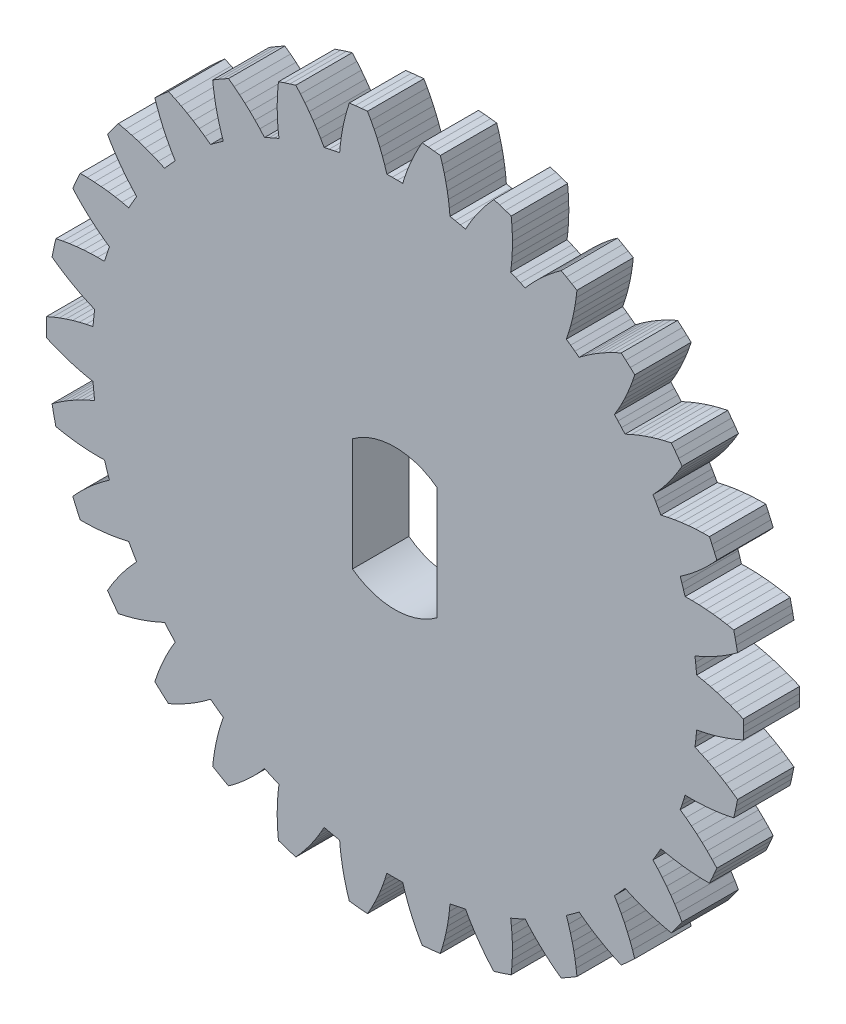
SolidWorks part; units mm, degrees
ref_plane "Front Plane" through (0, 0, 0) normal (0, 0, 1) x (1, 0, 0)
ref_plane "Top Plane" through (0, 0, 0) normal (0, 1, 0) x (1, 0, 0)
ref_plane "Right Plane" through (0, 0, 0) normal (1, 0, 0) x (0, 0, -1)
sketch "Sketch2" plane through (0, 0, 0) normal (0, 0, 1) x (1, 0, 0)
  line L20 (0.2811, 27.0228) -> (0.3553, 27.2598)
  line L21 (0.3553, 27.2598) -> (0.4378, 27.494)
  line L22 (0.4378, 27.494) -> (0.5284, 27.7252)
  line L23 (0.5284, 27.7252) -> (0.6271, 27.953)
  line L24 (0.6271, 27.953) -> (0.7337, 28.1773)
  line L25 (0.7337, 28.1773) -> (0.8481, 28.3976)
  line L26 (0.8481, 28.3976) -> (0.9702, 28.6139)
  line L27 (1.1852, 28.5951) -> (0.9702, 28.6139)
  line L28 (1.3998, 28.5725) -> (1.1852, 28.5951)
  line L29 (1.614, 28.5462) -> (1.3998, 28.5725)
  line L30 (1.614, 28.5462) -> (1.6885, 28.3093)
  line L31 (1.6885, 28.3093) -> (1.7546, 28.07)
  line L32 (1.7546, 28.07) -> (1.8122, 27.8285)
  line L33 (1.8122, 27.8285) -> (1.8614, 27.5851)
  line L34 (1.8614, 27.5851) -> (1.9019, 27.3401)
  line L35 (1.9019, 27.3401) -> (1.9339, 27.0939)
  line L36 (1.9339, 27.0939) -> (1.9572, 26.8467)
  line L37 (1.9572, 26.8467) -> (2.1412, 26.8109)
  line L38 (2.1412, 26.8109) -> (2.3246, 26.7719)
  line L39 (2.3246, 26.7719) -> (2.5072, 26.7298)
  line L41 (2.5072, 26.7298) -> (2.6291, 26.9461)
  line L42 (2.6291, 26.9461) -> (2.7584, 27.1581)
  line L43 (2.7584, 27.1581) -> (2.8951, 27.3653)
  line L44 (2.8951, 27.3653) -> (3.039, 27.5677)
  line L45 (3.039, 27.5677) -> (3.1899, 27.7649)
  line L46 (3.1899, 27.7649) -> (3.3476, 27.9567)
  line L47 (3.3476, 27.9567) -> (3.512, 28.1428)
  line L48 (3.7184, 28.0797) -> (3.512, 28.1428)
  line L49 (3.9236, 28.013) -> (3.7184, 28.0797)
  line L50 (4.1277, 27.9427) -> (3.9236, 28.013)
  line L51 (4.1277, 27.9427) -> (4.1513, 27.6955)
  line L52 (4.1513, 27.6955) -> (4.1661, 27.4477)
  line L53 (4.1661, 27.4477) -> (4.1723, 27.1995)
  line L54 (4.1723, 27.1995) -> (4.1698, 26.9512)
  line L55 (4.1698, 26.9512) -> (4.1586, 26.7031)
  line L56 (4.1586, 26.7031) -> (4.1386, 26.4556)
  line L57 (4.1386, 26.4556) -> (4.11, 26.209)
  line L58 (4.11, 26.209) -> (4.2826, 26.1357)
  line L59 (4.2826, 26.1357) -> (4.4538, 26.0595)
  line L60 (4.4538, 26.0595) -> (4.6237, 25.9803)
  line L61 (4.6237, 25.9803) -> (4.7879, 26.1666)
  line L62 (4.7879, 26.1666) -> (4.9585, 26.347)
  line L63 (4.9585, 26.347) -> (5.1353, 26.5213)
  line L64 (5.1353, 26.5213) -> (5.3181, 26.6893)
  line L65 (5.3181, 26.6893) -> (5.5067, 26.8508)
  line L66 (5.5067, 26.8508) -> (5.7008, 27.0056)
  line L67 (5.7008, 27.0056) -> (5.9003, 27.1535)
  line L68 (6.0891, 27.0489) -> (5.9003, 27.1535)
  line L69 (6.276, 26.941) -> (6.0891, 27.0489)
  line L70 (6.461, 26.8298) -> (6.276, 26.941)
  line L71 (6.461, 26.8298) -> (6.4326, 26.5831)
  line L72 (6.4326, 26.5831) -> (6.3956, 26.3376)
  line L73 (6.3956, 26.3376) -> (6.3501, 26.0935)
  line L74 (6.3501, 26.0935) -> (6.296, 25.8512)
  line L75 (6.296, 25.8512) -> (6.2334, 25.6109)
  line L76 (6.2334, 25.6109) -> (6.1625, 25.3729)
  line L77 (6.1625, 25.3729) -> (6.0832, 25.1376)
  line L78 (6.0832, 25.1376) -> (6.2368, 25.0301)
  line L79 (6.2368, 25.0301) -> (6.3884, 24.9199)
  line L80 (6.3884, 24.9199) -> (6.5381, 24.8071)
  line L81 (6.5381, 24.8071) -> (6.7374, 24.9552)
  line L82 (6.7374, 24.9552) -> (6.9418, 25.0962)
  line L83 (6.9418, 25.0962) -> (7.151, 25.23)
  line L84 (7.151, 25.23) -> (7.3648, 25.3563)
  line L85 (7.3648, 25.3563) -> (7.5828, 25.4751)
  line L86 (7.5828, 25.4751) -> (7.8049, 25.5861)
  line L87 (7.8049, 25.5861) -> (8.0307, 25.6893)
  line L88 (8.1936, 25.5477) -> (8.0307, 25.6893)
  line L89 (8.354, 25.4033) -> (8.1936, 25.5477)
  line L90 (8.5118, 25.2561) -> (8.354, 25.4033)
  line L91 (8.5118, 25.2561) -> (8.4328, 25.0207)
  line L92 (8.4328, 25.0207) -> (8.3456, 24.7882)
  line L93 (8.3456, 24.7882) -> (8.2503, 24.559)
  line L94 (8.2503, 24.559) -> (8.147, 24.3332)
  line L95 (8.147, 24.3332) -> (8.0359, 24.1111)
  line L96 (8.0359, 24.1111) -> (7.917, 23.8931)
  line L97 (7.917, 23.8931) -> (7.7905, 23.6794)
  line L98 (7.7905, 23.6794) -> (7.9184, 23.5424)
  line L99 (7.9184, 23.5424) -> (8.0438, 23.4031)
  line L100 (8.0438, 23.4031) -> (8.1668, 23.2616)
  line L101 (8.1668, 23.2616) -> (8.3925, 23.365)
  line L102 (8.3925, 23.365) -> (8.6217, 23.4604)
  line L103 (8.6217, 23.4604) -> (8.8542, 23.5478)
  line L104 (8.8542, 23.5478) -> (9.0895, 23.6269)
  line L105 (9.0895, 23.6269) -> (9.3275, 23.6977)
  line L106 (9.3275, 23.6977) -> (9.5678, 23.7602)
  line L107 (9.5678, 23.7602) -> (9.8102, 23.8141)
  line L108 (9.9401, 23.6418) -> (9.8102, 23.8141)
  line L109 (10.0669, 23.4672) -> (9.9401, 23.6418)
  line L110 (10.1907, 23.2904) -> (10.0669, 23.4672)
  line L111 (10.1907, 23.2904) -> (10.0645, 23.0766)
  line L112 (10.0645, 23.0766) -> (9.9309, 22.8673)
  line L113 (9.9309, 22.8673) -> (9.79, 22.6629)
  line L114 (9.79, 22.6629) -> (9.642, 22.4635)
  line L115 (9.642, 22.4635) -> (9.4871, 22.2694)
  line L116 (9.4871, 22.2694) -> (9.3255, 22.0809)
  line L117 (9.3255, 22.0809) -> (9.1574, 21.8981)
  line L118 (9.1574, 21.8981) -> (9.2539, 21.7375)
  line L119 (9.2539, 21.7375) -> (9.3476, 21.5751)
  line L120 (9.3476, 21.5751) -> (9.4385, 21.4112)
  line L121 (9.4385, 21.4112) -> (9.6808, 21.4654)
  line L122 (9.6808, 21.4654) -> (9.9249, 21.5111)
  line L123 (9.9249, 21.5111) -> (10.1704, 21.5482)
  line L124 (10.1704, 21.5482) -> (10.4171, 21.5767)
  line L125 (10.4171, 21.5767) -> (10.6646, 21.5965)
  line L126 (10.6646, 21.5965) -> (10.9126, 21.6076)
  line L127 (10.9126, 21.6076) -> (11.1609, 21.61)
  line L128 (11.2521, 21.4144) -> (11.1609, 21.61)
  line L129 (11.3399, 21.2172) -> (11.2521, 21.4144)
  line L130 (11.4242, 21.0186) -> (11.3399, 21.2172)
  line L131 (11.4242, 21.0186) -> (11.2563, 20.8357)
  line L132 (11.2563, 20.8357) -> (11.0821, 20.6588)
  line L133 (11.0821, 20.6588) -> (10.9017, 20.4881)
  line L134 (10.9017, 20.4881) -> (10.7155, 20.3238)
  line L135 (10.7155, 20.3238) -> (10.5237, 20.1662)
  line L136 (10.5237, 20.1662) -> (10.3264, 20.0154)
  line L137 (10.3264, 20.0154) -> (10.124, 19.8716)
  line L138 (10.124, 19.8716) -> (10.185, 19.6944)
  line L139 (10.185, 19.6944) -> (10.2429, 19.5161)
  line L140 (10.2429, 19.5161) -> (10.2977, 19.3368)
  line L141 (10.2977, 19.3368) -> (10.546, 19.3395)
  line L142 (10.546, 19.3395) -> (10.7943, 19.3334)
  line L143 (10.7943, 19.3334) -> (11.0421, 19.3187)
  line L144 (11.0421, 19.3187) -> (11.2893, 19.2952)
  line L145 (11.2893, 19.2952) -> (11.5355, 19.2631)
  line L146 (11.5355, 19.2631) -> (11.7805, 19.2224)
  line L147 (11.7805, 19.2224) -> (12.0238, 19.1732)
  line L148 (12.0724, 18.9629) -> (12.0238, 19.1732)
  line L149 (12.1172, 18.7518) -> (12.0724, 18.9629)
  line L150 (12.1584, 18.5399) -> (12.1172, 18.7518)
  line L151 (12.1584, 18.5399) -> (11.9561, 18.3959)
  line L152 (11.9561, 18.3959) -> (11.7489, 18.2591)
  line L153 (11.7489, 18.2591) -> (11.5371, 18.1297)
  line L154 (11.5371, 18.1297) -> (11.3208, 18.0077)
  line L155 (11.3208, 18.0077) -> (11.1003, 17.8934)
  line L156 (11.1003, 17.8934) -> (10.876, 17.7869)
  line L157 (10.876, 17.7869) -> (10.6481, 17.6884)
  line L158 (10.6481, 17.6884) -> (10.671, 17.5023)
  line L159 (10.671, 17.5023) -> (10.6906, 17.3159)
  line L160 (10.6906, 17.3159) -> (10.7069, 17.1291)
  line L161 (10.7069, 17.1291) -> (10.9503, 17.0801)
  line L162 (10.9503, 17.0801) -> (11.1919, 17.0226)
  line L163 (11.1919, 17.0226) -> (11.4312, 16.9566)
  line L164 (11.4312, 16.9566) -> (11.6682, 16.8823)
  line L165 (11.6682, 16.8823) -> (11.9023, 16.7997)
  line L166 (11.9023, 16.7997) -> (12.1335, 16.709)
  line L167 (12.1335, 16.709) -> (12.3613, 16.6102)
  line L168 (12.365, 16.3944) -> (12.3613, 16.6102)
  line L169 (12.365, 16.1786) -> (12.365, 16.3944)
  line L170 (12.3613, 15.9628) -> (12.365, 16.1786)
  line L171 (12.3613, 15.9628) -> (12.1335, 15.864)
  line L172 (12.1335, 15.864) -> (11.9023, 15.7733)
  line L173 (11.9023, 15.7733) -> (11.6682, 15.6907)
  line L174 (11.6682, 15.6907) -> (11.4312, 15.6164)
  line L175 (11.4312, 15.6164) -> (11.1919, 15.5504)
  line L176 (11.1919, 15.5504) -> (10.9503, 15.4929)
  line L177 (10.9503, 15.4929) -> (10.7069, 15.4438)
  line L178 (10.7069, 15.4438) -> (10.6906, 15.2571)
  line L179 (10.6906, 15.2571) -> (10.671, 15.0707)
  line L180 (10.671, 15.0707) -> (10.6481, 14.8846)
  line L181 (10.6481, 14.8846) -> (10.876, 14.7861)
  line L182 (10.876, 14.7861) -> (11.1003, 14.6796)
  line L183 (11.1003, 14.6796) -> (11.3208, 14.5653)
  line L184 (11.3208, 14.5653) -> (11.5371, 14.4433)
  line L185 (11.5371, 14.4433) -> (11.7489, 14.3139)
  line L186 (11.7489, 14.3139) -> (11.9561, 14.1771)
  line L187 (11.9561, 14.1771) -> (12.1584, 14.0331)
  line L188 (12.1172, 13.8212) -> (12.1584, 14.0331)
  line L189 (12.0724, 13.6101) -> (12.1172, 13.8212)
  line L190 (12.0238, 13.3998) -> (12.0724, 13.6101)
  line L191 (12.0238, 13.3998) -> (11.7805, 13.3506)
  line L192 (11.7805, 13.3506) -> (11.5355, 13.3098)
  line L193 (11.5355, 13.3098) -> (11.2893, 13.2778)
  line L194 (11.2893, 13.2778) -> (11.0421, 13.2543)
  line L195 (11.0421, 13.2543) -> (10.7943, 13.2396)
  line L196 (10.7943, 13.2396) -> (10.546, 13.2335)
  line L197 (10.546, 13.2335) -> (10.2977, 13.2362)
  line L198 (10.2977, 13.2362) -> (10.2429, 13.0569)
  line L199 (10.2429, 13.0569) -> (10.185, 12.8786)
  line L200 (10.185, 12.8786) -> (10.124, 12.7014)
  line L201 (10.124, 12.7014) -> (10.3264, 12.5576)
  line L202 (10.3264, 12.5576) -> (10.5237, 12.4068)
  line L203 (10.5237, 12.4068) -> (10.7155, 12.2492)
  line L204 (10.7155, 12.2492) -> (10.9017, 12.0849)
  line L205 (10.9017, 12.0849) -> (11.0821, 11.9142)
  line L206 (11.0821, 11.9142) -> (11.2563, 11.7373)
  line L207 (11.2563, 11.7373) -> (11.4242, 11.5544)
  line L208 (11.3399, 11.3558) -> (11.4242, 11.5544)
  line L209 (11.2521, 11.1586) -> (11.3399, 11.3558)
  line L210 (11.1609, 10.963) -> (11.2521, 11.1586)
  line L211 (11.1609, 10.963) -> (10.9126, 10.9654)
  line L212 (10.9126, 10.9654) -> (10.6646, 10.9765)
  line L213 (10.6646, 10.9765) -> (10.4171, 10.9963)
  line L214 (10.4171, 10.9963) -> (10.1704, 11.0248)
  line L215 (10.1704, 11.0248) -> (9.9249, 11.0619)
  line L216 (9.9249, 11.0619) -> (9.6808, 11.1076)
  line L217 (9.6808, 11.1076) -> (9.4385, 11.1618)
  line L218 (9.4385, 11.1618) -> (9.3476, 10.9979)
  line L219 (9.3476, 10.9979) -> (9.2539, 10.8355)
  line L220 (9.2539, 10.8355) -> (9.1574, 10.6748)
  line L221 (9.1574, 10.6748) -> (9.3255, 10.4921)
  line L222 (9.3255, 10.4921) -> (9.4871, 10.3036)
  line L223 (9.4871, 10.3036) -> (9.642, 10.1095)
  line L224 (9.642, 10.1095) -> (9.79, 9.9101)
  line L225 (9.79, 9.9101) -> (9.9309, 9.7057)
  line L226 (9.9309, 9.7057) -> (10.0645, 9.4964)
  line L227 (10.0645, 9.4964) -> (10.1907, 9.2826)
  line L228 (10.0669, 9.1058) -> (10.1907, 9.2826)
  line L229 (9.9401, 8.9312) -> (10.0669, 9.1058)
  line L230 (9.8102, 8.7589) -> (9.9401, 8.9312)
  line L231 (9.8102, 8.7589) -> (9.5678, 8.8128)
  line L232 (9.5678, 8.8128) -> (9.3275, 8.8753)
  line L233 (9.3275, 8.8753) -> (9.0895, 8.9461)
  line L234 (9.0895, 8.9461) -> (8.8542, 9.0252)
  line L235 (8.8542, 9.0252) -> (8.6217, 9.1126)
  line L236 (8.6217, 9.1126) -> (8.3925, 9.208)
  line L237 (8.3925, 9.208) -> (8.1668, 9.3114)
  line L238 (8.1668, 9.3114) -> (8.0438, 9.1699)
  line L239 (8.0438, 9.1699) -> (7.9184, 9.0306)
  line L240 (7.9184, 9.0306) -> (7.7905, 8.8936)
  line L241 (7.7905, 8.8936) -> (7.917, 8.6799)
  line L242 (7.917, 8.6799) -> (8.0359, 8.4619)
  line L243 (8.0359, 8.4619) -> (8.147, 8.2398)
  line L244 (8.147, 8.2398) -> (8.2503, 8.014)
  line L245 (8.2503, 8.014) -> (8.3456, 7.7848)
  line L246 (8.3456, 7.7848) -> (8.4328, 7.5523)
  line L247 (8.4328, 7.5523) -> (8.5118, 7.3169)
  line L248 (8.354, 7.1697) -> (8.5118, 7.3169)
  line L249 (8.1936, 7.0253) -> (8.354, 7.1697)
  line L250 (8.0307, 6.8837) -> (8.1936, 7.0253)
  line L251 (8.0307, 6.8837) -> (7.8049, 6.9869)
  line L252 (7.8049, 6.9869) -> (7.5828, 7.0979)
  line L253 (7.5828, 7.0979) -> (7.3647, 7.2167)
  line L254 (7.3647, 7.2167) -> (7.151, 7.343)
  line L255 (7.151, 7.343) -> (6.9418, 7.4768)
  line L256 (6.9418, 7.4768) -> (6.7374, 7.6178)
  line L257 (6.7374, 7.6178) -> (6.5381, 7.7659)
  line L258 (6.5381, 7.7659) -> (6.3884, 7.6531)
  line L259 (6.3884, 7.6531) -> (6.2368, 7.5429)
  line L260 (6.2368, 7.5429) -> (6.0832, 7.4354)
  line L261 (6.0832, 7.4354) -> (6.1625, 7.2)
  line L262 (6.1625, 7.2) -> (6.2334, 6.9621)
  line L263 (6.2334, 6.9621) -> (6.296, 6.7218)
  line L264 (6.296, 6.7218) -> (6.3501, 6.4795)
  line L265 (6.3501, 6.4795) -> (6.3956, 6.2354)
  line L266 (6.3956, 6.2354) -> (6.4326, 5.9899)
  line L267 (6.4326, 5.9899) -> (6.4609, 5.7432)
  line L268 (6.276, 5.632) -> (6.4609, 5.7432)
  line L269 (6.0891, 5.5241) -> (6.276, 5.632)
  line L270 (5.9003, 5.4195) -> (6.0891, 5.5241)
  line L271 (5.9003, 5.4195) -> (5.7008, 5.5674)
  line L272 (5.7008, 5.5674) -> (5.5067, 5.7222)
  line L273 (5.5067, 5.7222) -> (5.3181, 5.8837)
  line L274 (5.3181, 5.8837) -> (5.1353, 6.0517)
  line L275 (5.1353, 6.0517) -> (4.9585, 6.226)
  line L276 (4.9585, 6.226) -> (4.7879, 6.4064)
  line L277 (4.7879, 6.4064) -> (4.6237, 6.5927)
  line L278 (4.6237, 6.5927) -> (4.4538, 6.5135)
  line L279 (4.4538, 6.5135) -> (4.2826, 6.4372)
  line L280 (4.2826, 6.4372) -> (4.11, 6.364)
  line L281 (4.11, 6.364) -> (4.1386, 6.1174)
  line L282 (4.1386, 6.1174) -> (4.1585, 5.8699)
  line L283 (4.1585, 5.8699) -> (4.1698, 5.6218)
  line L284 (4.1698, 5.6218) -> (4.1723, 5.3735)
  line L285 (4.1723, 5.3735) -> (4.1661, 5.1253)
  line L286 (4.1661, 5.1253) -> (4.1512, 4.8775)
  line L287 (4.1512, 4.8775) -> (4.1277, 4.6303)
  line L288 (3.9236, 4.56) -> (4.1277, 4.6303)
  line L289 (3.7184, 4.4933) -> (3.9236, 4.56)
  line L290 (3.512, 4.4302) -> (3.7184, 4.4933)
  line L291 (3.512, 4.4302) -> (3.3476, 4.6163)
  line L292 (3.3476, 4.6163) -> (3.1899, 4.8081)
  line L293 (3.1899, 4.8081) -> (3.039, 5.0053)
  line L294 (3.039, 5.0053) -> (2.8951, 5.2076)
  line L295 (2.8951, 5.2076) -> (2.7584, 5.4149)
  line L296 (2.7584, 5.4149) -> (2.629, 5.6269)
  line L297 (2.629, 5.6269) -> (2.5072, 5.8432)
  line L298 (2.5072, 5.8432) -> (2.3246, 5.8011)
  line L299 (2.3246, 5.8011) -> (2.1412, 5.7621)
  line L300 (2.1412, 5.7621) -> (1.9572, 5.7263)
  line L301 (1.9572, 5.7263) -> (1.9339, 5.4791)
  line L302 (1.9339, 5.4791) -> (1.9019, 5.2329)
  line L303 (1.9019, 5.2329) -> (1.8613, 4.9879)
  line L304 (1.8613, 4.9879) -> (1.8122, 4.7445)
  line L305 (1.8122, 4.7445) -> (1.7545, 4.503)
  line L306 (1.7545, 4.503) -> (1.6885, 4.2637)
  line L307 (1.6885, 4.2637) -> (1.614, 4.0268)
  line L308 (1.3998, 4.0005) -> (1.614, 4.0268)
  line L309 (1.1852, 3.9779) -> (1.3998, 4.0005)
  line L310 (0.9702, 3.9591) -> (1.1852, 3.9779)
  line L311 (0.9702, 3.9591) -> (0.8481, 4.1754)
  line L312 (0.8481, 4.1754) -> (0.7337, 4.3957)
  line L313 (0.7337, 4.3957) -> (0.6271, 4.62)
  line L314 (0.6271, 4.62) -> (0.5284, 4.8478)
  line L315 (0.5284, 4.8478) -> (0.4378, 5.079)
  line L316 (0.4378, 5.079) -> (0.3553, 5.3132)
  line L317 (0.3553, 5.3132) -> (0.2811, 5.5502)
  line L318 (0.2811, 5.5502) -> (0.0937, 5.5469)
  line L319 (0.0937, 5.5469) -> (-0.0937, 5.5469)
  line L320 (-0.0937, 5.5469) -> (-0.2811, 5.5502)
  line L321 (-0.2811, 5.5502) -> (-0.3553, 5.3132)
  line L322 (-0.3553, 5.3132) -> (-0.4378, 5.079)
  line L323 (-0.4378, 5.079) -> (-0.5284, 4.8478)
  line L324 (-0.5284, 4.8478) -> (-0.6271, 4.62)
  line L325 (-0.6271, 4.62) -> (-0.7337, 4.3957)
  line L326 (-0.7337, 4.3957) -> (-0.8481, 4.1754)
  line L327 (-0.8481, 4.1754) -> (-0.9702, 3.9591)
  line L328 (-1.1852, 3.9779) -> (-0.9702, 3.9591)
  line L329 (-1.3998, 4.0005) -> (-1.1852, 3.9779)
  line L330 (-1.614, 4.0268) -> (-1.3998, 4.0005)
  line L331 (-1.614, 4.0268) -> (-1.6885, 4.2637)
  line L332 (-1.6885, 4.2637) -> (-1.7546, 4.503)
  line L333 (-1.7546, 4.503) -> (-1.8122, 4.7445)
  line L334 (-1.8122, 4.7445) -> (-1.8614, 4.9879)
  line L335 (-1.8614, 4.9879) -> (-1.9019, 5.2329)
  line L336 (-1.9019, 5.2329) -> (-1.9339, 5.4791)
  line L337 (-1.9339, 5.4791) -> (-1.9572, 5.7263)
  line L338 (-1.9572, 5.7263) -> (-2.1412, 5.7621)
  line L339 (-2.1412, 5.7621) -> (-2.3246, 5.8011)
  line L340 (-2.3246, 5.8011) -> (-2.5072, 5.8432)
  line L341 (-2.5072, 5.8432) -> (-2.6291, 5.6269)
  line L342 (-2.6291, 5.6269) -> (-2.7584, 5.4149)
  line L343 (-2.7584, 5.4149) -> (-2.8951, 5.2077)
  line L344 (-2.8951, 5.2077) -> (-3.039, 5.0053)
  line L345 (-3.039, 5.0053) -> (-3.1899, 4.8081)
  line L346 (-3.1899, 4.8081) -> (-3.3476, 4.6163)
  line L347 (-3.3476, 4.6163) -> (-3.512, 4.4302)
  line L348 (-3.7184, 4.4933) -> (-3.512, 4.4302)
  line L349 (-3.9236, 4.56) -> (-3.7184, 4.4933)
  line L350 (-4.1277, 4.6303) -> (-3.9236, 4.56)
  line L351 (-4.1277, 4.6303) -> (-4.1513, 4.8775)
  line L352 (-4.1513, 4.8775) -> (-4.1661, 5.1253)
  line L353 (-4.1661, 5.1253) -> (-4.1723, 5.3735)
  line L354 (-4.1723, 5.3735) -> (-4.1698, 5.6218)
  line L355 (-4.1698, 5.6218) -> (-4.1586, 5.8699)
  line L356 (-4.1586, 5.8699) -> (-4.1386, 6.1174)
  line L357 (-4.1386, 6.1174) -> (-4.11, 6.364)
  line L358 (-4.11, 6.364) -> (-4.2826, 6.4372)
  line L359 (-4.2826, 6.4372) -> (-4.4538, 6.5135)
  line L360 (-4.4538, 6.5135) -> (-4.6237, 6.5927)
  line L361 (-4.6237, 6.5927) -> (-4.7879, 6.4064)
  line L362 (-4.7879, 6.4064) -> (-4.9585, 6.226)
  line L363 (-4.9585, 6.226) -> (-5.1353, 6.0517)
  line L364 (-5.1353, 6.0517) -> (-5.3181, 5.8837)
  line L365 (-5.3181, 5.8837) -> (-5.5067, 5.7222)
  line L366 (-5.5067, 5.7222) -> (-5.7008, 5.5674)
  line L367 (-5.7008, 5.5674) -> (-5.9003, 5.4195)
  line L368 (-6.0891, 5.5241) -> (-5.9003, 5.4195)
  line L369 (-6.276, 5.632) -> (-6.0891, 5.5241)
  line L370 (-6.461, 5.7432) -> (-6.276, 5.632)
  line L371 (-6.461, 5.7432) -> (-6.4326, 5.9899)
  line L372 (-6.4326, 5.9899) -> (-6.3956, 6.2354)
  line L373 (-6.3956, 6.2354) -> (-6.3501, 6.4795)
  line L374 (-6.3501, 6.4795) -> (-6.296, 6.7218)
  line L375 (-6.296, 6.7218) -> (-6.2334, 6.9621)
  line L376 (-6.2334, 6.9621) -> (-6.1625, 7.2)
  line L377 (-6.1625, 7.2) -> (-6.0832, 7.4354)
  line L378 (-6.0832, 7.4354) -> (-6.2368, 7.5429)
  line L379 (-6.2368, 7.5429) -> (-6.3884, 7.6531)
  line L380 (-6.3884, 7.6531) -> (-6.5381, 7.7659)
  line L381 (-6.5381, 7.7659) -> (-6.7374, 7.6178)
  line L382 (-6.7374, 7.6178) -> (-6.9418, 7.4768)
  line L383 (-6.9418, 7.4768) -> (-7.151, 7.343)
  line L384 (-7.151, 7.343) -> (-7.3648, 7.2167)
  line L385 (-7.3648, 7.2167) -> (-7.5828, 7.0979)
  line L386 (-7.5828, 7.0979) -> (-7.8049, 6.9869)
  line L387 (-7.8049, 6.9869) -> (-8.0307, 6.8837)
  line L388 (-8.1936, 7.0253) -> (-8.0307, 6.8837)
  line L389 (-8.354, 7.1697) -> (-8.1936, 7.0253)
  line L390 (-8.5118, 7.3169) -> (-8.354, 7.1697)
  line L391 (-8.5118, 7.3169) -> (-8.4328, 7.5523)
  line L392 (-8.4328, 7.5523) -> (-8.3456, 7.7848)
  line L393 (-8.3456, 7.7848) -> (-8.2503, 8.014)
  line L394 (-8.2503, 8.014) -> (-8.147, 8.2398)
  line L395 (-8.147, 8.2398) -> (-8.0359, 8.4619)
  line L396 (-8.0359, 8.4619) -> (-7.917, 8.6799)
  line L397 (-7.917, 8.6799) -> (-7.7905, 8.8936)
  line L398 (-7.7905, 8.8936) -> (-7.9184, 9.0306)
  line L399 (-7.9184, 9.0306) -> (-8.0438, 9.1699)
  line L400 (-8.0438, 9.1699) -> (-8.1668, 9.3114)
  line L401 (-8.1668, 9.3114) -> (-8.3925, 9.208)
  line L402 (-8.3925, 9.208) -> (-8.6218, 9.1126)
  line L403 (-8.6218, 9.1126) -> (-8.8542, 9.0252)
  line L404 (-8.8542, 9.0252) -> (-9.0895, 8.9461)
  line L405 (-9.0895, 8.9461) -> (-9.3275, 8.8753)
  line L406 (-9.3275, 8.8753) -> (-9.5678, 8.8128)
  line L407 (-9.5678, 8.8128) -> (-9.8102, 8.7589)
  line L408 (-9.9401, 8.9312) -> (-9.8102, 8.7589)
  line L409 (-10.0669, 9.1058) -> (-9.9401, 8.9312)
  line L410 (-10.1907, 9.2826) -> (-10.0669, 9.1058)
  line L411 (-10.1907, 9.2826) -> (-10.0645, 9.4964)
  line L412 (-10.0645, 9.4964) -> (-9.9309, 9.7057)
  line L413 (-9.9309, 9.7057) -> (-9.79, 9.9101)
  line L414 (-9.79, 9.9101) -> (-9.642, 10.1095)
  line L415 (-9.642, 10.1095) -> (-9.4871, 10.3036)
  line L416 (-9.4871, 10.3036) -> (-9.3255, 10.4921)
  line L417 (-9.3255, 10.4921) -> (-9.1574, 10.6749)
  line L418 (-9.1574, 10.6749) -> (-9.2539, 10.8355)
  line L419 (-9.2539, 10.8355) -> (-9.3476, 10.9979)
  line L420 (-9.3476, 10.9979) -> (-9.4385, 11.1618)
  line L421 (-9.4385, 11.1618) -> (-9.6808, 11.1076)
  line L422 (-9.6808, 11.1076) -> (-9.9249, 11.0619)
  line L423 (-9.9249, 11.0619) -> (-10.1704, 11.0248)
  line L424 (-10.1704, 11.0248) -> (-10.4171, 10.9963)
  line L425 (-10.4171, 10.9963) -> (-10.6646, 10.9765)
  line L426 (-10.6646, 10.9765) -> (-10.9126, 10.9654)
  line L427 (-10.9126, 10.9654) -> (-11.1609, 10.963)
  line L428 (-11.2521, 11.1586) -> (-11.1609, 10.963)
  line L429 (-11.3399, 11.3558) -> (-11.2521, 11.1586)
  line L430 (-11.4242, 11.5544) -> (-11.3399, 11.3558)
  line L431 (-11.4242, 11.5544) -> (-11.2563, 11.7373)
  line L432 (-11.2563, 11.7373) -> (-11.0821, 11.9142)
  line L433 (-11.0821, 11.9142) -> (-10.9017, 12.0849)
  line L434 (-10.9017, 12.0849) -> (-10.7155, 12.2492)
  line L435 (-10.7155, 12.2492) -> (-10.5237, 12.4068)
  line L436 (-10.5237, 12.4068) -> (-10.3264, 12.5576)
  line L437 (-10.3264, 12.5576) -> (-10.124, 12.7014)
  line L438 (-10.124, 12.7014) -> (-10.185, 12.8786)
  line L439 (-10.185, 12.8786) -> (-10.243, 13.0569)
  line L440 (-10.243, 13.0569) -> (-10.2978, 13.2362)
  line L441 (-10.2978, 13.2362) -> (-10.546, 13.2335)
  line L442 (-10.546, 13.2335) -> (-10.7943, 13.2396)
  line L443 (-10.7943, 13.2396) -> (-11.0421, 13.2543)
  line L444 (-11.0421, 13.2543) -> (-11.2893, 13.2778)
  line L445 (-11.2893, 13.2778) -> (-11.5355, 13.3099)
  line L446 (-11.5355, 13.3099) -> (-11.7805, 13.3506)
  line L447 (-11.7805, 13.3506) -> (-12.0238, 13.3998)
  line L448 (-12.0724, 13.6101) -> (-12.0238, 13.3998)
  line L449 (-12.1173, 13.8212) -> (-12.0724, 13.6101)
  line L450 (-12.1584, 14.0331) -> (-12.1173, 13.8212)
  line L451 (-12.1584, 14.0331) -> (-11.9562, 14.1771)
  line L452 (-11.9562, 14.1771) -> (-11.7489, 14.3139)
  line L453 (-11.7489, 14.3139) -> (-11.5371, 14.4433)
  line L454 (-11.5371, 14.4433) -> (-11.3208, 14.5653)
  line L455 (-11.3208, 14.5653) -> (-11.1004, 14.6796)
  line L456 (-11.1004, 14.6796) -> (-10.876, 14.7861)
  line L457 (-10.876, 14.7861) -> (-10.6481, 14.8846)
  line L458 (-10.6481, 14.8846) -> (-10.671, 15.0707)
  line L459 (-10.671, 15.0707) -> (-10.6906, 15.2571)
  line L460 (-10.6906, 15.2571) -> (-10.7069, 15.4438)
  line L461 (-10.7069, 15.4438) -> (-10.9503, 15.4929)
  line L462 (-10.9503, 15.4929) -> (-11.1919, 15.5504)
  line L463 (-11.1919, 15.5504) -> (-11.4313, 15.6164)
  line L464 (-11.4313, 15.6164) -> (-11.6682, 15.6907)
  line L465 (-11.6682, 15.6907) -> (-11.9023, 15.7733)
  line L466 (-11.9023, 15.7733) -> (-12.1335, 15.864)
  line L467 (-12.1335, 15.864) -> (-12.3613, 15.9628)
  line L468 (-12.365, 16.1786) -> (-12.3613, 15.9628)
  line L469 (-12.365, 16.3944) -> (-12.365, 16.1786)
  line L470 (-12.3613, 16.6102) -> (-12.365, 16.3944)
  line L471 (-12.3613, 16.6102) -> (-12.1335, 16.709)
  line L472 (-12.1335, 16.709) -> (-11.9023, 16.7997)
  line L473 (-11.9023, 16.7997) -> (-11.6682, 16.8823)
  line L474 (-11.6682, 16.8823) -> (-11.4313, 16.9566)
  line L475 (-11.4313, 16.9566) -> (-11.1919, 17.0226)
  line L476 (-11.1919, 17.0226) -> (-10.9503, 17.0801)
  line L477 (-10.9503, 17.0801) -> (-10.7069, 17.1292)
  line L478 (-10.7069, 17.1292) -> (-10.6906, 17.3159)
  line L479 (-10.6906, 17.3159) -> (-10.671, 17.5023)
  line L480 (-10.671, 17.5023) -> (-10.6481, 17.6884)
  line L481 (-10.6481, 17.6884) -> (-10.876, 17.7869)
  line L482 (-10.876, 17.7869) -> (-11.1004, 17.8934)
  line L483 (-11.1004, 17.8934) -> (-11.3208, 18.0077)
  line L484 (-11.3208, 18.0077) -> (-11.5371, 18.1297)
  line L485 (-11.5371, 18.1297) -> (-11.7489, 18.2591)
  line L486 (-11.7489, 18.2591) -> (-11.9561, 18.3959)
  line L487 (-11.9561, 18.3959) -> (-12.1584, 18.5399)
  line L488 (-12.1173, 18.7518) -> (-12.1584, 18.5399)
  line L489 (-12.0724, 18.9629) -> (-12.1173, 18.7518)
  line L490 (-12.0238, 19.1732) -> (-12.0724, 18.9629)
  line L491 (-12.0238, 19.1732) -> (-11.7805, 19.2224)
  line L492 (-11.7805, 19.2224) -> (-11.5355, 19.2632)
  line L493 (-11.5355, 19.2632) -> (-11.2893, 19.2952)
  line L494 (-11.2893, 19.2952) -> (-11.0421, 19.3187)
  line L495 (-11.0421, 19.3187) -> (-10.7943, 19.3334)
  line L496 (-10.7943, 19.3334) -> (-10.546, 19.3395)
  line L497 (-10.546, 19.3395) -> (-10.2978, 19.3368)
  line L498 (-10.2978, 19.3368) -> (-10.2429, 19.5161)
  line L499 (-10.2429, 19.5161) -> (-10.185, 19.6944)
  line L500 (-10.185, 19.6944) -> (-10.124, 19.8716)
  line L501 (-10.124, 19.8716) -> (-10.3264, 20.0154)
  line L502 (-10.3264, 20.0154) -> (-10.5237, 20.1662)
  line L503 (-10.5237, 20.1662) -> (-10.7155, 20.3238)
  line L504 (-10.7155, 20.3238) -> (-10.9017, 20.4881)
  line L505 (-10.9017, 20.4881) -> (-11.0821, 20.6588)
  line L506 (-11.0821, 20.6588) -> (-11.2563, 20.8357)
  line L507 (-11.2563, 20.8357) -> (-11.4242, 21.0186)
  line L508 (-11.3399, 21.2172) -> (-11.4242, 21.0186)
  line L509 (-11.2521, 21.4144) -> (-11.3399, 21.2172)
  line L510 (-11.1609, 21.61) -> (-11.2521, 21.4144)
  line L511 (-11.1609, 21.61) -> (-10.9126, 21.6076)
  line L512 (-10.9126, 21.6076) -> (-10.6646, 21.5965)
  line L513 (-10.6646, 21.5965) -> (-10.4171, 21.5767)
  line L514 (-10.4171, 21.5767) -> (-10.1704, 21.5482)
  line L515 (-10.1704, 21.5482) -> (-9.9249, 21.5111)
  line L516 (-9.9249, 21.5111) -> (-9.6808, 21.4654)
  line L517 (-9.6808, 21.4654) -> (-9.4385, 21.4112)
  line L518 (-9.4385, 21.4112) -> (-9.3476, 21.5751)
  line L519 (-9.3476, 21.5751) -> (-9.2539, 21.7375)
  line L520 (-9.2539, 21.7375) -> (-9.1574, 21.8981)
  line L521 (-9.1574, 21.8981) -> (-9.3255, 22.0809)
  line L522 (-9.3255, 22.0809) -> (-9.4871, 22.2694)
  line L523 (-9.4871, 22.2694) -> (-9.642, 22.4635)
  line L524 (-9.642, 22.4635) -> (-9.79, 22.6629)
  line L525 (-9.79, 22.6629) -> (-9.9309, 22.8673)
  line L526 (-9.9309, 22.8673) -> (-10.0645, 23.0766)
  line L527 (-10.0645, 23.0766) -> (-10.1907, 23.2904)
  line L528 (-10.0669, 23.4672) -> (-10.1907, 23.2904)
  line L529 (-9.9401, 23.6418) -> (-10.0669, 23.4672)
  line L530 (-9.8102, 23.8141) -> (-9.9401, 23.6418)
  line L531 (-9.8102, 23.8141) -> (-9.5678, 23.7602)
  line L532 (-9.5678, 23.7602) -> (-9.3275, 23.6977)
  line L533 (-9.3275, 23.6977) -> (-9.0895, 23.6269)
  line L534 (-9.0895, 23.6269) -> (-8.8542, 23.5478)
  line L535 (-8.8542, 23.5478) -> (-8.6217, 23.4604)
  line L536 (-8.6217, 23.4604) -> (-8.3925, 23.365)
  line L537 (-8.3925, 23.365) -> (-8.1668, 23.2616)
  line L538 (-8.1668, 23.2616) -> (-8.0438, 23.4031)
  line L539 (-8.0438, 23.4031) -> (-7.9184, 23.5424)
  line L540 (-7.9184, 23.5424) -> (-7.7905, 23.6794)
  line L541 (-7.7905, 23.6794) -> (-7.917, 23.8931)
  line L542 (-7.917, 23.8931) -> (-8.0359, 24.1111)
  line L543 (-8.0359, 24.1111) -> (-8.147, 24.3332)
  line L544 (-8.147, 24.3332) -> (-8.2503, 24.559)
  line L545 (-8.2503, 24.559) -> (-8.3456, 24.7882)
  line L546 (-8.3456, 24.7882) -> (-8.4328, 25.0207)
  line L547 (-8.4328, 25.0207) -> (-8.5118, 25.2561)
  line L548 (-8.354, 25.4033) -> (-8.5118, 25.2561)
  line L549 (-8.1936, 25.5477) -> (-8.354, 25.4033)
  line L550 (-8.0307, 25.6893) -> (-8.1936, 25.5477)
  line L551 (-8.0307, 25.6893) -> (-7.8049, 25.5861)
  line L552 (-7.8049, 25.5861) -> (-7.5828, 25.4751)
  line L553 (-7.5828, 25.4751) -> (-7.3648, 25.3563)
  line L554 (-7.3648, 25.3563) -> (-7.151, 25.23)
  line L555 (-7.151, 25.23) -> (-6.9418, 25.0962)
  line L556 (-6.9418, 25.0962) -> (-6.7374, 24.9552)
  line L557 (-6.7374, 24.9552) -> (-6.5381, 24.8071)
  line L558 (-6.5381, 24.8071) -> (-6.3884, 24.9199)
  line L559 (-6.3884, 24.9199) -> (-6.2368, 25.0301)
  line L560 (-6.2368, 25.0301) -> (-6.0832, 25.1376)
  line L561 (-6.0832, 25.1376) -> (-6.1625, 25.373)
  line L562 (-6.1625, 25.373) -> (-6.2334, 25.6109)
  line L563 (-6.2334, 25.6109) -> (-6.296, 25.8512)
  line L564 (-6.296, 25.8512) -> (-6.3501, 26.0935)
  line L565 (-6.3501, 26.0935) -> (-6.3956, 26.3376)
  line L566 (-6.3956, 26.3376) -> (-6.4326, 26.5831)
  line L567 (-6.4326, 26.5831) -> (-6.461, 26.8298)
  line L568 (-6.276, 26.941) -> (-6.461, 26.8298)
  line L569 (-6.0891, 27.0489) -> (-6.276, 26.941)
  line L570 (-5.9003, 27.1535) -> (-6.0891, 27.0489)
  line L571 (-5.9003, 27.1535) -> (-5.7008, 27.0056)
  line L572 (-5.7008, 27.0056) -> (-5.5067, 26.8508)
  line L573 (-5.5067, 26.8508) -> (-5.3181, 26.6893)
  line L574 (-5.3181, 26.6893) -> (-5.1353, 26.5213)
  line L575 (-5.1353, 26.5213) -> (-4.9585, 26.347)
  line L576 (-4.9585, 26.347) -> (-4.7879, 26.1666)
  line L577 (-4.7879, 26.1666) -> (-4.6237, 25.9803)
  line L578 (-4.6237, 25.9803) -> (-4.4538, 26.0595)
  line L579 (-4.4538, 26.0595) -> (-4.2826, 26.1358)
  line L580 (-4.2826, 26.1358) -> (-4.11, 26.209)
  line L581 (-4.11, 26.209) -> (-4.1386, 26.4556)
  line L582 (-4.1386, 26.4556) -> (-4.1586, 26.7031)
  line L583 (-4.1586, 26.7031) -> (-4.1698, 26.9512)
  line L584 (-4.1698, 26.9512) -> (-4.1723, 27.1995)
  line L585 (-4.1723, 27.1995) -> (-4.1661, 27.4477)
  line L586 (-4.1661, 27.4477) -> (-4.1513, 27.6955)
  line L587 (-4.1513, 27.6955) -> (-4.1277, 27.9427)
  line L588 (-3.9236, 28.013) -> (-4.1277, 27.9427)
  line L589 (-3.7184, 28.0797) -> (-3.9236, 28.013)
  line L590 (-3.512, 28.1428) -> (-3.7184, 28.0797)
  line L591 (-3.512, 28.1428) -> (-3.3476, 27.9567)
  line L592 (-3.3476, 27.9567) -> (-3.1899, 27.7649)
  line L593 (-3.1899, 27.7649) -> (-3.039, 27.5677)
  line L594 (-3.039, 27.5677) -> (-2.8951, 27.3653)
  line L595 (-2.8951, 27.3653) -> (-2.7584, 27.1581)
  line L596 (-2.7584, 27.1581) -> (-2.6291, 26.9461)
  line L597 (-2.6291, 26.9461) -> (-2.5072, 26.7298)
  line L598 (-2.5072, 26.7298) -> (-2.3246, 26.7719)
  line L599 (-2.3246, 26.7719) -> (-2.1412, 26.8109)
  line L600 (-2.1412, 26.8109) -> (-1.9572, 26.8467)
  line L601 (-1.9572, 26.8467) -> (-1.9339, 27.0939)
  line L602 (-1.9339, 27.0939) -> (-1.9019, 27.3401)
  line L603 (-1.9019, 27.3401) -> (-1.8614, 27.5851)
  line L604 (-1.8614, 27.5851) -> (-1.8122, 27.8285)
  line L605 (-1.8122, 27.8285) -> (-1.7546, 28.07)
  line L606 (-1.7546, 28.07) -> (-1.6885, 28.3093)
  line L607 (-1.6885, 28.3093) -> (-1.614, 28.5462)
  line L608 (-1.3998, 28.5725) -> (-1.614, 28.5462)
  line L609 (-1.1852, 28.5951) -> (-1.3998, 28.5725)
  line L610 (-0.9702, 28.6139) -> (-1.1852, 28.5951)
  line L611 (-0.9702, 28.6139) -> (-0.8481, 28.3976)
  line L612 (-0.8481, 28.3976) -> (-0.7337, 28.1773)
  line L613 (-0.7337, 28.1773) -> (-0.6271, 27.953)
  line L614 (-0.6271, 27.953) -> (-0.5284, 27.7252)
  line L615 (-0.5284, 27.7252) -> (-0.4378, 27.494)
  line L616 (-0.4378, 27.494) -> (-0.3553, 27.2598)
  line L617 (-0.3553, 27.2598) -> (-0.2811, 27.0228)
  line L618 (-0.2811, 27.0228) -> (-0.0937, 27.0261)
  line L619 (-0.0937, 27.0261) -> (0.0937, 27.0261)
  line L620 (0.0937, 27.0261) -> (0.2811, 27.0228)
  circle A0 centre (0, 16.2865) radius 10.74 construction
  point P638 (0, 16.2865)
  dimension "D1" = 30
extrude "Boss-Extrude1" add sketch "Sketch2" along normal blind 2
sketch "Sketch3" plane through (0, 0, 2) normal (0, 0, 1) x (1, 0, 0)
  line L0 (-1.5, 18.2865) -> (-1.5, 14.2865)
  line L1 (-1.5, 16.2865) -> (1.5, 16.2865) construction
  line L2 (1.5, 18.2865) -> (1.5, 14.2865)
  arc A0 (-1.5, 14.2865) -> (1.5, 14.2865) centre (0, 16.2865) ccw
  arc A1 (1.5, 18.2865) -> (-1.5, 18.2865) centre (0, 16.2865) ccw
  point P0 (0, 16.2865)
  dimension "D1" = 5
  dimension "D2" = 3
extrude "Cut-Extrude1" cut sketch "Sketch3" against normal up to next
